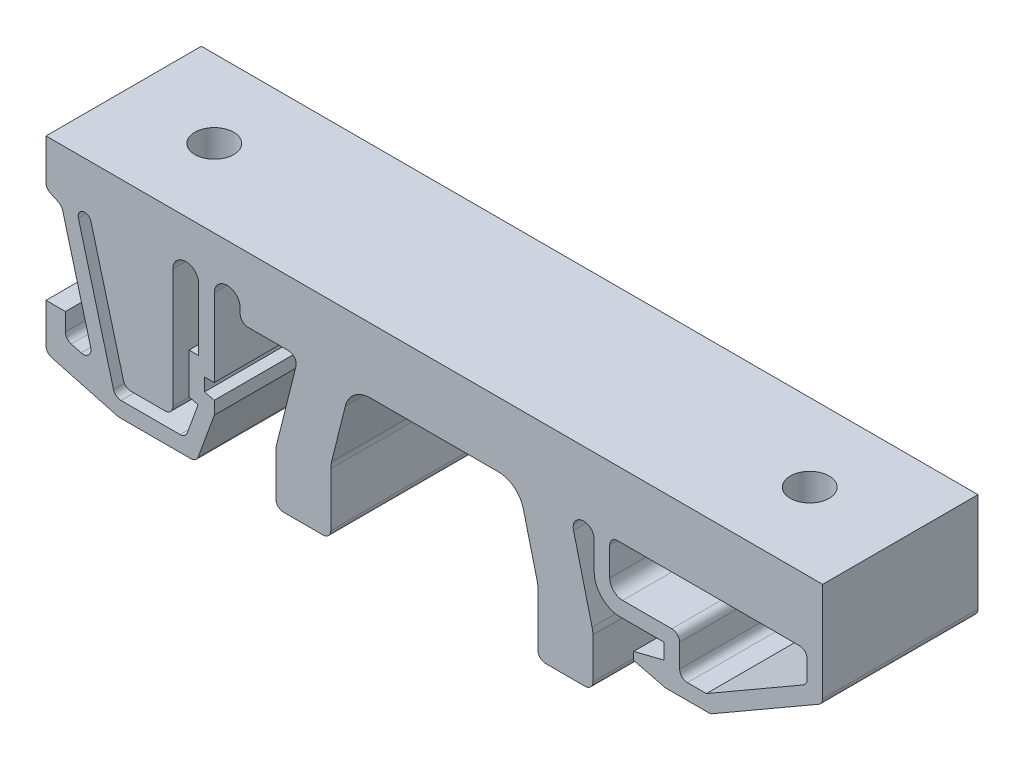
SolidWorks part; units mm, degrees
material "ABS"
ref_plane "Front Plane" through (0, 0, 0) normal (0, 0, 1) x (1, 0, 0)
ref_plane "Top Plane" through (0, 0, 0) normal (0, 1, 0) x (1, 0, 0)
ref_plane "Right Plane" through (0, 0, 0) normal (1, 0, 0) x (0, 0, -1)
sketch "Sketch2" plane through (0, 0, 0) normal (0, 0, 1) x (1, 0, 0)
  line L0 (0, 22.5226) -> (0, -8.8845) construction
  line L1 (6.5, 11) -> (-6.5, 11)
  line L2 (-6.5, 11) -> (-8, 4.9838)
  line L3 (-8, 4.9838) -> (-8, 0)
  line L4 (-8, 0) -> (-12.25, 0)
  line L5 (-12.25, 0) -> (-12.25, 3.9811)
  line L6 (-12.25, 3.9811) -> (-10.5, 11)
  line L7 (-10.5, 11) -> (-15, 11)
  line L8 (-15, 11) -> (-15, 13)
  line L9 (-15, 13) -> (-17, 13)
  line L10 (-17, 13) -> (-17, 6)
  line L11 (-17, 6) -> (-17.75, 6)
  line L12 (-17.75, 6) -> (-17.75, 5)
  line L13 (-17.75, 5) -> (-17, 4.813)
  line L14 (-17, 4.813) -> (-17, 3.813)
  line L15 (-17, 3.813) -> (-18.3878, 0)
  line L16 (-18.3878, 0) -> (-24.3878, 0)
  line L17 (-24.3878, 0) -> (-30, 1.5038)
  line L18 (-30, 1.5038) -> (-30, 5.0038)
  line L19 (-30, 5.0038) -> (-28.5, 5.0038)
  line L20 (-28.5, 5.0038) -> (-28.5, 3.1724)
  line L21 (-28.5, 3.1724) -> (-26.2784, 2.5771)
  line L22 (-26.2784, 2.5771) -> (-28.7854, 11.9336)
  line L23 (-28.7854, 11.9336) -> (-30, 12.5)
  line L24 (-30, 12.5) -> (-30, 16)
  line L25 (-30, 16) -> (0, 16)
  line L30 (-8, 0) -> (0, 0) construction
  line L32 (10.5, 11) -> (12.35, 11)
  line L33 (12.25, 3.9811) -> (10.5, 11)
  line L34 (12.25, 0) -> (12.25, 3.9811)
  line L35 (8, 0) -> (12.25, 0)
  line L36 (8, 4.9838) -> (8, 0)
  line L37 (6.5, 11) -> (8, 4.9838)
  line L38 (12.35, 11) -> (12.35, 6)
  line L40 (12.35, 6) -> (17.75, 6)
  line L41 (17.75, 6) -> (17.75, 4.8)
  line L42 (17.75, 4.8) -> (15.4, 4.2141)
  line L43 (15.4, 4.2141) -> (15.4, 3.6083)
  line L44 (15.4, 3.6083) -> (17.8397, 3)
  line L45 (17.8397, 3) -> (21.3397, 3)
  line L46 (21.3397, 3) -> (30, 8)
  line L47 (30, 8) -> (30, 16)
  line L48 (30, 16) -> (0, 16)
  line L49 (-17.75, 6) -> (0, 6) construction
  line L50 (0, 6) -> (17.75, 6) construction
  line L54 (15.4, 3.9112) -> (22.918, 3.9112) construction
  line L56 (-8, 0) -> (8, 0) construction
  point P37 (0, 11)
  dimension "D1" = 5
  dimension "D2" = 16
  dimension "D3" = 104
  dimension "D4" = 16
  dimension "D5" = 13
  dimension "D6" = 24.5
  dimension "D7" = 4
  dimension "D8" = 2
  dimension "D9" = 2
  dimension "D10" = 4.5
  dimension "D11" = 35.5
  dimension "D12" = 7
  dimension "D13" = 1
  dimension "D14" = 1
  dimension "D15" = 20
  dimension "D16" = 6
  dimension "D17" = 15
  dimension "D18" = 1.5
  dimension "D19" = 3.5
  dimension "D20" = 2
  dimension "D21" = 60
  dimension "D22" = 60
  dimension "D23" = 50
  dimension "D24" = 3.5
  dimension "D25" = 2.3
  dimension "D26" = 60
  dimension "D27" = 8
  dimension "D28" = 15.4
  dimension "D29" = 3.5
  dimension "D30" = 1.2
  dimension "D31" = 5.4
  dimension "D32" = 3
extrude "Boss-Extrude1" add sketch "Sketch2" along normal mid plane 12
sketch "Sketch3" plane through (0, 0, 0) normal (0, 0, 1) x (1, 0, 0)
  line L0 (-27.6263, 12.2442) -> (-24.667, 1.2)
  line L1 (-24.667, 1.2) -> (-19.2281, 1.2)
  line L2 (-19.2281, 1.2) -> (-18.2498, 3.8879)
  line L3 (-18.2498, 3.8879) -> (-18.95, 4.0625)
  line L4 (-18.95, 4.0625) -> (-18.95, 7.2)
  line L5 (-18.95, 7.2) -> (-18.2, 7.2)
  line L6 (-18.2, 7.2) -> (-18.2, 13)
  line L7 (-18.2, 13) -> (-20.2, 13)
  line L8 (-20.2, 13) -> (-20.2, 2.2)
  line L9 (-20.2, 2.2) -> (-23.8997, 2.2)
  line L10 (-23.8997, 2.2) -> (-26.6604, 12.503)
  line L11 (-26.6604, 12.503) -> (-27.6263, 12.2442)
  line L12 (13.55, 11) -> (13.55, 7.2)
  line L13 (13.55, 7.2) -> (18.95, 7.2)
  line L14 (18.95, 7.2) -> (18.95, 4.2)
  line L15 (18.95, 4.2) -> (21.0182, 4.2)
  line L16 (21.0182, 4.2) -> (28.8, 8.6928)
  line L17 (28.8, 8.6928) -> (28.8, 11)
  line L18 (28.8, 11) -> (13.55, 11)
  line L19 (-28.7854, 11.9336) -> (-26.2784, 2.5771) construction
  line L20 (-18.3878, 0) -> (-17, 3.813) construction
  line L21 (-24.3878, 0) -> (-18.3878, 0) construction
  line L22 (-17.75, 5) -> (-17.75, 6) construction
  line L23 (-17, 6) -> (-17, 13) construction
  line L26 (-17, 4.813) -> (-17.75, 5) construction
  line L27 (-17.75, 6) -> (-17, 6) construction
  line L28 (-17, 13) -> (-15, 13) construction
  line L29 (12.35, 11) -> (12.35, 6) construction
  line L30 (12.35, 6) -> (17.75, 6) construction
  line L31 (17.75, 6) -> (17.75, 4.8) construction
  line L32 (30, 8) -> (30, 16) construction
  line L33 (21.3397, 3) -> (30, 8) construction
  line L34 (17.8397, 3) -> (21.3397, 3) construction
  line L35 (10.5, 11) -> (12.35, 11) construction
  dimension "D1" = 1.2
  dimension "D2" = 1.2
  dimension "D3" = 1.2
  dimension "D4" = 1.2
  dimension "D5" = 1.2
  dimension "D6" = 2
  dimension "D7" = 1
  dimension "D8" = 1.2
  dimension "D9" = 1.2
  dimension "D10" = 1.2
  dimension "D11" = 1.2
  dimension "D12" = 1.2
  dimension "D13" = 1.2
  dimension "D14" = 1.2
  dimension "D15" = 1.2
  dimension "D16" = 1
extrude "Cut-Extrude1" cut sketch "Sketch3" against normal through all both and the other way through all
fillet "Fillet1" radius 2 1 edges at (12.35, 6, 0)
fillet "Fillet2" radius 1 1 edges at (13.55, 7.2, 0)
fillet "Fillet3" 2 edges at (10.5, 11, 0) (12.35, 11, 0) type full round first side face at (11.375, 7.4906, 0) second side face at (12.35, 9.5, 0) middle face at (11.425, 11, 0)
fillet "Fillet4" radius 2 6 edges at (-12.25, 3.9811, 0) (12.25, 3.9811, 0) (8, 4.9838, 0) (-8, 4.9838, 0) (-6.5, 11, 0) (6.5, 11, 0)
fillet "Fillet5" 2 edges at (-20.2, 13, 0) (-18.2, 13, 0) type full round first side face at (-20.2, 7.6, 0) second side face at (-18.2, 10.1, 0) middle face at (-19.2, 13, 0)
fillet "Fillet6" 2 edges at (-17, 13, 0) (-15, 13, 0) type full round first side face at (-17, 9.5, 0) second side face at (-15, 12, 0) middle face at (-16, 13, 0)
fillet "Fillet7" 2 edges at (-27.6263, 12.2442, 0) (-26.6604, 12.503, 0) type full round first side face at (-26.1467, 6.7221, 0) second side face at (-25.2801, 7.3515, 0) middle face at (-27.1434, 12.3736, 0)
fillet "Fillet8" radius 0.6 25 edges at (-10.5, 11, 0) (-12.25, 0, 0) (-8, 0, 0) (8, 0, 0) (12.25, 0, 0) (17.8397, 3, 0) (28.8, 8.6928, 0) (28.8, 11, 0) (13.55, 11, 0) (18.95, 7.2, 0) (18.95, 4.2, 0) (21.3397, 3, 0) (30, 8, 0) (-23.8997, 2.2, 0) (-20.2, 2.2, 0) (-30, 1.5038, 0) (-28.5, 3.1724, 0) (-26.2784, 2.5771, 0) (-24.667, 1.2, 0) (-19.2281, 1.2, 0) (-24.3878, 0, 0) (-18.3878, 0, 0) (-15, 11, 0) (-30, 12.5, 0) (-28.7854, 11.9336, 0)
sketch "Sketch4" plane through (0, 16, 0) normal (0, 1, 0) x (1, 0, 0)
  line L0 (0, 0) -> (-23, 0) construction
  line L3 (0, 0) -> (0, -6) construction
  line L4 (30, -6) -> (-30, -6) construction
  circle A0 centre (-23, 0) radius 1.5
  circle A1 centre (23, 0) radius 1.5
  dimension "D1" = 3
  dimension "D2" = 46
extrude "Cut-Extrude2" cut sketch "Sketch4" against normal blind 8.5
